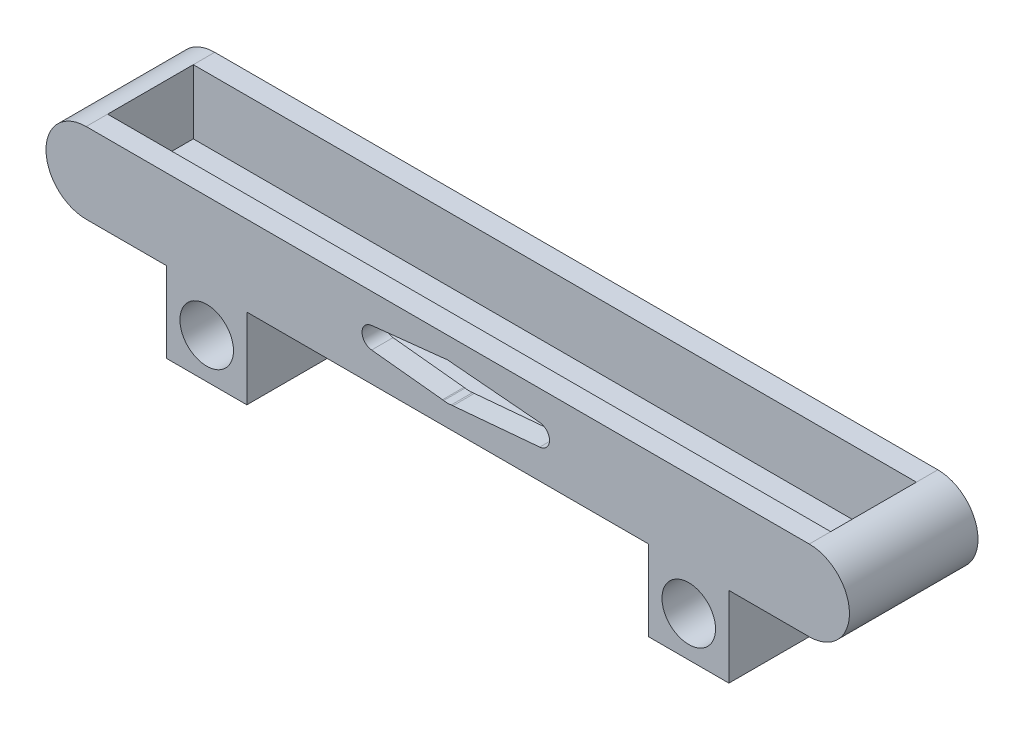
SolidWorks part; units mm, degrees
ref_plane "Front Plane" through (0, 0, 0) normal (0, 0, 1) x (1, 0, 0)
ref_plane "Top Plane" through (0, 0, 0) normal (0, 1, 0) x (1, 0, 0)
ref_plane "Right Plane" through (0, 0, 0) normal (1, 0, 0) x (0, 0, -1)
sketch "Sketch1" plane through (0, 0, 0) normal (0, 0, 1) x (1, 0, 0)
  line L0 (67.5, 0) -> (-67.5, 0) construction
  line L1 (67.5, -7.5) -> (-67.5, -7.5)
  line L2 (67.5, 7.5) -> (-67.5, 7.5)
  line L3 (0, 7.5) -> (0, -7.5) construction
  line L4 (-0.9651, 3.3974) -> (-14.2115, 1.9888)
  line L9 (0.9668, 3.4151) -> (17.1749, 1.9923)
  line L10 (0.9668, -3.4151) -> (17.1749, -1.9923)
  line L11 (-0.9651, -3.3974) -> (-14.2115, -1.9888)
  line L12 (0, 7.5) -> (0, -40.1867) construction
  line L13 (-52.5, -22.5) -> (-37.5, -22.5)
  line L14 (-52.5, -22.5) -> (-52.5, -7.5)
  line L15 (-52.5, -7.5) -> (-37.5, -7.5)
  line L16 (-37.5, -22.5) -> (-37.5, -7.5)
  line L17 (-52.5, -22.5) -> (-37.5, -7.5) construction
  line L18 (-52.5, -7.5) -> (-37.5, -22.5) construction
  line L19 (52.5, -7.5) -> (37.5, -7.5)
  line L20 (37.5, -22.5) -> (37.5, -7.5)
  line L21 (52.5, -22.5) -> (37.5, -22.5)
  line L22 (52.5, -22.5) -> (52.5, -7.5)
  arc A0 (67.5, -7.5) -> (67.5, 7.5) centre (67.5, 0) ccw
  arc A1 (-67.5, 7.5) -> (-67.5, -7.5) centre (-67.5, 0) ccw
  arc A6 (0.9668, 3.4151) -> (-0.9651, 3.3974) centre (0.0923, -6.5466) ccw
  arc A7 (-0.9651, -3.3974) -> (0.9668, -3.4151) centre (0.0923, 6.5466) ccw
  arc A8 (-14.2115, 1.9888) -> (-14.2115, -1.9888) centre (-14, 0) ccw
  arc A9 (17.1749, 1.9923) -> (17.1749, -1.9923) centre (17, 0) cw
  circle A10 centre (0, 0) radius 3.5
  circle A11 centre (0, 0) radius 2
  circle A12 centre (-45, -15) radius 5
  circle A13 centre (45, -15) radius 5
  point P2 (0, 0)
  point P8 (-45, -15)
  point P14 (19, 0)
  point P15 (-14, 0)
  point P16 (0, 3.5)
  point P17 (0, -3.5)
  point P30 (0, 3.5)
  point P33 (0, -3.5)
  point P41 (-45.4294, -15)
  dimension "D2" = 15
  dimension "D8" = 2
  dimension "D9" = 2
  dimension "D10" = 10
  dimension "D11" = 7
  dimension "D12" = 4
  dimension "D15" = 10
  dimension "D1" = 135
  dimension "D3" = 15
  dimension "D4" = 19
  dimension "D5" = 14
  dimension "D6" = 3.5
  dimension "D7" = 3.5
  dimension "D13" = 15
  dimension "D14" = 15
extrude "Boss-Extrude1" add sketch "Sketch1" along normal blind 4 contours L2 A1 L1 A0 A10 A6 L9 A9 L10 A7 L11 A8 L4 | L13 L16 L1 L14 | L21 L22 L1 L20 region at (60, -5.9925, 0) region at (52.2879, -15, 0) region at (-37.7121, -15, 0)
extrude "Boss-Extrude2" add sketch "Sketch1<4>" against normal blind 20 contours L2 A1 L1 A0 A10 A6 L9 A9 L10 A7 L11 A8 L4 | A10 A6 L4 A8 L11 A7 | A10 A7 L10 A9 L9 A6 | A6 A10 A7 A11 | A7 A10 | A11 | A6 A10 | L21 L22 L1 L20 | L13 L16 L1 L14 region at (60, -5.9925, 0) region at (52.2879, -15, 0) region at (-37.7121, -15, 0) region at (-8.6612, 0, 0) region at (-0.0489, 3.4663, 0) region at (-0.0473, 3.3541, 0) region at (10.0092, 0, 0) region at (-0.0489, -3.4663, 0) region at (0, 0, 0)
sketch "Sketch1<4>" plane through (0, 0, 0) normal (0, 0, 1) x (1, 0, 0) same geometry as "Sketch1"
sketch "Sketch2" plane through (0, 7.5, 0) normal (0, 1, 0) x (1, 0, 0)
  line L0 (67.5, -4) -> (-67.5, -4) construction
  line L1 (-67.5, 16) -> (67.5, 16)
  line L2 (-67.5, 16) -> (-67.5, 0)
  line L3 (-67.5, 0) -> (67.5, 0)
  line L4 (67.5, 16) -> (67.5, 0)
  line L5 (67.5, 20) -> (-67.5, 20) construction
  line L7 (-67.5, -4) -> (-67.5, 20) construction
  line L8 (67.5, -4) -> (67.5, 20) construction
  dimension "D1" = 4
  dimension "D2" = 4
extrude "Cut-Extrude1" cut sketch "Sketch2" against normal blind 12
